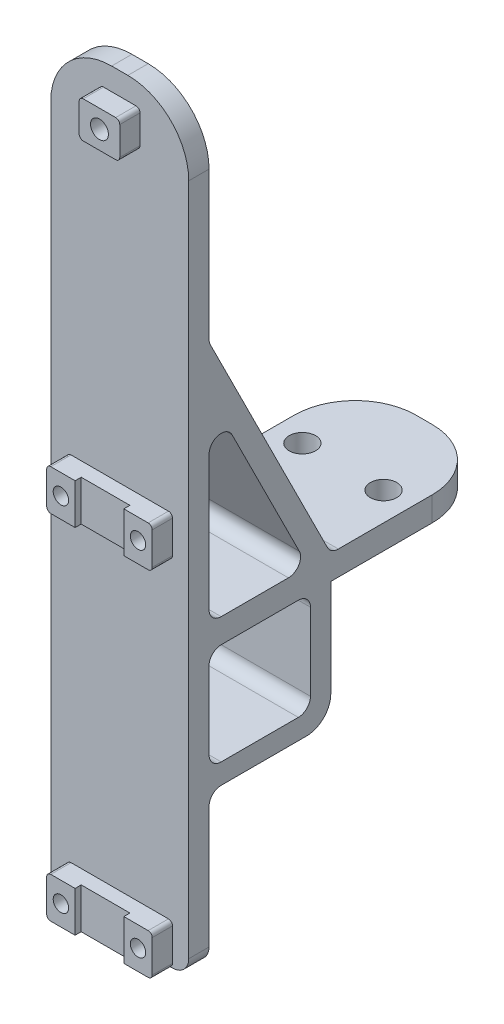
SolidWorks part; units mm, degrees
ref_plane "前视基准面" through (0, 0, 0) normal (0, 0, 1) x (1, 0, 0)
ref_plane "上视基准面" through (0, 0, 0) normal (0, 1, 0) x (1, 0, 0)
ref_plane "右视基准面" through (0, 0, 0) normal (1, 0, 0) x (0, 0, -1)
sketch "草图1" plane through (0, 0, 0) normal (0, 1, 0) x (1, 0, 0)
  line L1 (-17, 35) -> (17, 35)
  line L2 (-17, 35) -> (-17, -35)
  line L3 (-17, -35) -> (17, -35)
  line L4 (17, 35) -> (17, -35)
  line L5 (0, -35) -> (0, 35) construction
  line L6 (-17, 0) -> (17, 0) construction
  point P0 (0, 0)
  dimension "D1" = 70
  dimension "D2" = 34
extrude "凸台-拉伸1" add sketch "草图1" against normal blind 3 and the other way blind 3
sketch "草图3" plane through (0, 0, 35) normal (0, 0, 1) x (1, 0, 0)
  line L2 (-17, 115) -> (17, 115)
  line L3 (-17, 115) -> (-17, -115)
  line L4 (-17, -115) -> (17, -115)
  line L5 (17, 115) -> (17, -115)
  line L6 (0, -115) -> (0, 115) construction
  line L7 (-17, 0) -> (17, 0) construction
  point P2 (0, 0)
  dimension "D1" = 230
  dimension "D2" = 34
extrude "凸台-拉伸2" add sketch "草图3" along normal blind 5
sketch "草图4" plane through (0, -3, 0) normal (0, -1, 0) x (1, 0, 0)
  line L1 (17, 10) -> (-17, 10)
  line L2 (17, 5) -> (-17, 5)
  line L3 (17, 5) -> (-17, 5)
  line L4 (17, 10) -> (17, 5)
  line L5 (-17, 10) -> (-17, 5)
  dimension "D1" = 40
  dimension "D2" = 5
extrude "凸台-拉伸3" add sketch "草图4" along normal blind 30
sketch "草图6" plane through (0, -33, 0) normal (0, -1, 0) x (1, 0, 0)
  line L0 (17, 35) -> (-17, 35)
  line L1 (17, 35) -> (-17, 35)
  line L2 (-17, 10) -> (-17, 35) construction
  line L3 (17, 35) -> (-17, 35)
  line L4 (17, 35) -> (17, 5)
  line L5 (17, 5) -> (-20, 5)
  line L6 (-17, 35) -> (-20, 5)
  line L7 (-17, 10) -> (-17, 35)
  line M1 (17, 5) -> (17, 10)
  line M2 (17, 10) -> (-17, 10)
  line M3 (-17, 10) -> (-17, 5)
  line M4 (-17, 5) -> (17, 5)
extrude "凸台-拉伸4" add sketch "草图6" against normal blind 5 contours L1 L6 L4 M2 | M4 M1 M2 M3 region at (0, -33, 22.5) region at (0, -33, 7.5)
sketch "草图7" plane through (0, 0, 40) normal (0, 0, 1) x (1, 0, 0)
  line L0 (-45.7663, 0) -> (52.3831, 0) construction
  line L2 (0, 98.4579) -> (0, -85.1557) construction
  circle A0 centre (0, -105) radius 2.2
  circle A1 centre (0, 105) radius 2.2
  dimension "D1" = 4.4
  dimension "D2" = 105
extrude "切除-拉伸1" cut sketch "草图7" against normal through all
sketch "草图8" plane through (0, 0, 5) normal (0, 0, -1) x (-1, 0, 0)
  line L0 (-17, -18) -> (17, -18) construction
  line L1 (-17, -33) -> (-17, -3) construction
  line L2 (17, -33) -> (17, -3) construction
  line L3 (0, -3) -> (0, -33) construction
  line L4 (17, -3) -> (-17, -3) construction
  line L5 (17, -33) -> (-17, -33) construction
  circle A0 centre (0, -18) radius 3.2
  dimension "D1" = 6.4
extrude "切除-拉伸2" [suppressed] cut sketch "草图8" against normal up to next
sketch "草图9" plane through (0, -3, 0) normal (0, -1, 0) x (1, 0, 0)
  line L0 (0, 5) -> (0, -35) construction
  line L1 (-17, 5) -> (17, 5) construction
  line L2 (17, -35) -> (-17, -35) construction
  line L3 (17, -15) -> (-17, -15) construction
  line L4 (17, 5) -> (17, -35) construction
  line L5 (-17, -35) -> (-17, 5) construction
  circle A0 centre (0, -15) radius 3.25 construction
  circle A1 centre (10, -15) radius 3.25
  circle A2 centre (-10, -15) radius 3.25
  dimension "D1" = 6.5
  dimension "D2" = 6.5
  dimension "D3" = 10
extrude "切除-拉伸3" cut sketch "草图9" against normal through all
sketch "草图10" plane through (17, 0, 0) normal (1, 0, 0) x (0, 0, -1)
  line L0 (-35, 3) -> (-5, 3) construction
  line L1 (-35, 3) -> (35, 3) construction
  line L2 (-35, 51.8197) -> (-35, 63)
  line L3 (-35, 3) -> (-35, 115) construction
  line L4 (-35, 63) -> (-5, 3)
  line L5 (-35, 51.8197) -> (-10.5902, 3)
  line L6 (-39.4721, 60.7639) -> (-9.4721, 0.7639) construction
  line L7 (-5, 3) -> (-10.5902, 3)
  dimension "D1" = 30
  dimension "D2" = 60
  dimension "D3" = 5
extrude "凸台-拉伸5" add sketch "草图10" against normal up to surface (34 mm away) up to face at (-17, -6.6, 16)
fillet "圆角1" [suppressed] radius 2
sketch "草图11" plane through (0, 0, 40) normal (0, 0, 1) x (1, 0, 0)
  line L0 (0, 91.0726) -> (0, -60) construction
  line L1 (-10, 20) -> (-10, 15)
  line L2 (10, 20) -> (10, 15)
  line L3 (-13, 0) -> (-10, 0) construction
  line L4 (-13, -20) -> (-10, -20)
  line L5 (-13, 20) -> (-13, 15)
  line L6 (13, 20) -> (13, 15)
  line L7 (-13, 20) -> (-10, 20)
  line L8 (-13, -15) -> (-10, -15)
  line L9 (-13, 15) -> (-10, 15)
  line L10 (-28.9653, 20) -> (48.3087, 20) construction
  line L11 (-28.9653, 15) -> (48.3087, 15) construction
  line L12 (-28.9653, 0) -> (48.3087, 0) construction
  line L13 (-28.9653, -15) -> (48.3087, -15) construction
  line L14 (-28.9653, -20) -> (48.3087, -20) construction
  line L15 (-13, -60) -> (-10, -60)
  line L16 (-13, 20) -> (-10, 20)
  line L17 (13, 91.0726) -> (13, -88.4268) construction
  line L18 (-13, -55) -> (-10, -55)
  line L19 (10, 91.0726) -> (10, -88.4268) construction
  line L20 (0, 91.0726) -> (0, -88.4268) construction
  line L21 (-10, 91.0726) -> (-10, -88.4268) construction
  line L22 (-13, 91.0726) -> (-13, -88.4268) construction
  line L23 (10, -55) -> (13, -55)
  line L24 (-13, -55) -> (13, -55) construction
  line L25 (10, -60) -> (13, -60)
  line L26 (-13, -60) -> (13, -60) construction
  line L27 (10, -55) -> (10, -60)
  line L28 (13, -55) -> (13, -60)
  line L29 (-10, -55) -> (-10, -60)
  line L30 (-13, -55) -> (-13, -60)
  line L31 (13, -15) -> (13, -20)
  line L32 (10, -15) -> (10, -20)
  line L33 (-10, -15) -> (-10, -20)
  line L34 (-13, -15) -> (-13, -20)
  line L35 (10, -15) -> (13, -15)
  line L36 (10, -20) -> (13, -20)
  line L37 (-13, -20) -> (13, -20) construction
  line L38 (10, 20) -> (13, 20)
  line L39 (10, 20) -> (13, 20)
  line L40 (-13, 20) -> (13, 20) construction
  line L41 (10, 15) -> (13, 15)
  line L42 (10, 0) -> (13, 0) construction
  dimension "D3" = 20
  dimension "D4" = 3
  dimension "D5" = 3
  dimension "D6" = 20
  dimension "D7" = 15
  dimension "D8" = 15
  dimension "D9" = 40
  dimension "D12" = 5
extrude "切除-拉伸4" [suppressed] cut sketch "草图11" against normal up to next contours L5 L9 L1 L7 | L2 L41 L6 L38 | L32 L36 L31 L35 | L8 L34 L4 L33 | L18 L30 L15 L29 | L28 L23 L27 L25
sketch "草图12" plane through (0, 0, 40) normal (0, 0, 1) x (1, 0, 0)
  line L0 (17, -115) -> (17, 115) construction
  line L1 (17, -70) -> (-20, -70)
  line L2 (17, -70) -> (17, -122.3677)
  line L3 (17, -122.3677) -> (-20, -122.3677)
  line L4 (-20, -70) -> (-20, -122.3677)
  line L5 (-87.5049, 0) -> (82.6106, 0) construction
  dimension "D1" = 70
extrude "切除-拉伸5" cut sketch "草图12" against normal through all
sketch "草图13" plane through (0, 0, 40) normal (0, 0, 1) x (1, 0, 0)
  line L0 (0, 125.3929) -> (0, -99.238) construction
  line L1 (17, -70) -> (-17, -70) construction
  line L2 (-6, -60) -> (6, -60)
  line L3 (-6, -60) -> (-6, -70)
  line L4 (-6, -70) -> (6, -70)
  line L5 (6, -60) -> (6, -70)
  line L6 (0, -70) -> (0, -60) construction
  line L7 (-6, -65) -> (6, -65) construction
  line L8 (-6, 27) -> (6, 27)
  line L9 (-6, 17) -> (-6, 27)
  line L10 (6, 17) -> (6, 27)
  line L11 (-6, 17) -> (6, 17)
  line L12 (-36.441, 27) -> (36.1987, 27) construction
  line L13 (-36.441, 17) -> (36.1987, 17) construction
  line L15 (-5, 109.5) -> (5, 109.5)
  line L16 (-5, 109.5) -> (-5, 100.5)
  line L17 (-5, 100.5) -> (5, 100.5)
  line L18 (5, 109.5) -> (5, 100.5)
  line L19 (0, 100.5) -> (0, 109.5) construction
  line L20 (-5, 105) -> (5, 105) construction
  circle A0 centre (0, 105) radius 2.2 construction
  circle A1 centre (0, 105) radius 2.2
  point P3 (0, -65)
  point P17 (0, 105)
  dimension "D1" = 10
  dimension "D2" = 12
  dimension "D3" = 97
  dimension "D5" = 6
  dimension "D6" = 6
  dimension "D7" = 9
  dimension "D8" = 10
  dimension "D4" = 10
extrude "凸台-拉伸6" add sketch "草图13" along normal blind 3.5
sketch "草图14" plane through (0, 0, 43.5) normal (0, 0, 1) x (1, 0, 0)
  line L4 (5, 100.5) -> (5, 109.5)
  line L5 (5, 109.5) -> (-5, 109.5)
  line L6 (-5, 109.5) -> (-5, 100.5)
  line L7 (-5, 100.5) -> (5, 100.5)
  line L8 (5, 100.5) -> (5, 109.5)
  line L9 (5, 109.5) -> (-5, 109.5)
  line L10 (-5, 109.5) -> (-5, 100.5)
  line L11 (-5, 100.5) -> (5, 100.5)
  circle A0 centre (0, 105) radius 2.2 construction
  circle A1 centre (0, 105) radius 2.2
  dimension "D1" = 0
extrude "凸台-拉伸7" add sketch "草图14" along normal blind 1.5
sketch "草图15" plane through (0, 0, 40) normal (0, 0, 1) x (1, 0, 0)
  line L0 (0, 120.2577) -> (0, -90.0496) construction
  line L1 (-6, 27) -> (-13, 27)
  line L2 (-6, 27) -> (-6, 17)
  line L3 (-6, 17) -> (-13, 17)
  line L4 (-13, 27) -> (-13, 17)
  line L5 (-9.5, 27) -> (-9.5, 17) construction
  line L6 (-6, -70) -> (-13, -70)
  line L7 (-6, -70) -> (-6, -60)
  line L8 (-6, -60) -> (-13, -60)
  line L9 (-13, -70) -> (-13, -60)
  line L10 (-9.5, -60) -> (-9.5, -70) construction
  line L11 (9.5, 27) -> (9.5, 17) construction
  line L12 (13, 27) -> (13, 17)
  line L13 (6, 17) -> (13, 17)
  line L14 (6, 27) -> (6, 17)
  line L15 (6, 27) -> (13, 27)
  line L16 (9.5, -60) -> (9.5, -70) construction
  line L17 (13, -70) -> (13, -60)
  line L18 (6, -60) -> (13, -60)
  line L19 (6, -70) -> (6, -60)
  line L20 (6, -70) -> (13, -70)
  circle A0 centre (-9.5, 22) radius 1.9
  circle A1 centre (-9.5, -65) radius 1.9
  circle A2 centre (9.5, 22) radius 1.9
  circle A3 centre (9.5, -65) radius 1.9
  dimension "D5" = 3.8
  dimension "D6" = 3.8
  dimension "D1" = 10
  dimension "D2" = 7
  dimension "D3" = 10
  dimension "D4" = 7
extrude "凸台-拉伸8" add sketch "草图15" along normal blind 5
fillet "圆角2" radius 15 4 edges at (17, 115, 37.5) (-17, 115, 37.5) (-17, 0, -35) (17, 0, -35)
fillet "圆角3" radius 4 2 edges at (-17, -70, 37.5) (17, -70, 37.5)
fillet "圆角4" radius 3 10 edges at (0, -33, 35) (0, -28, 35) (0, -3, 35) (0, -3, 10) (0, -28, 10) (0, 3, 10.5902) (0, 51.8197, 35) (0, 3, 35) (0, 63, 35) (0, 3, 5)
fillet "圆角5" radius 6 1 edges at (0, -33, 5)
fillet "圆角6" radius 1 12 edges at (-5, 100.5, 42.5) (5, 100.5, 42.5) (-5, 109.5, 42.5) (5, 109.5, 42.5) (13, -70, 42.5) (-13, -60, 42.5) (-13, -70, 42.5) (13, -60, 42.5) (13, 17, 42.5) (-13, 17, 42.5) (-13, 27, 42.5) (13, 27, 42.5)
